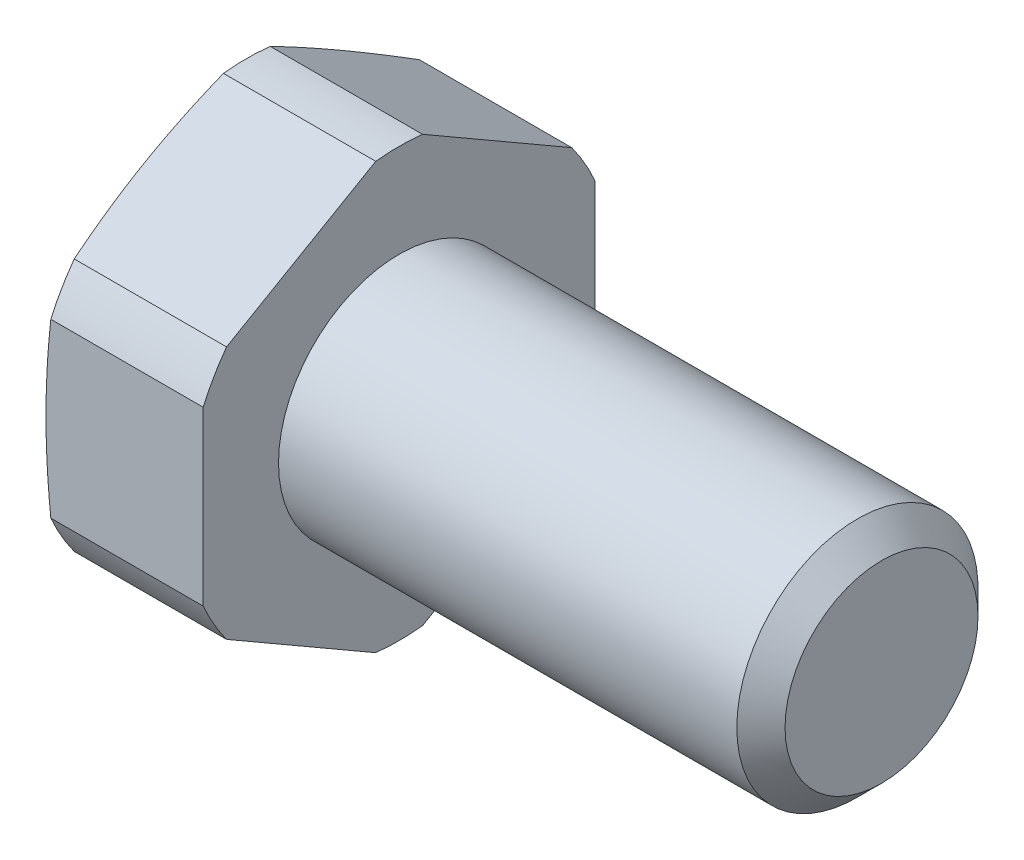
SolidWorks part; units mm, degrees
material "AISI 1020"
ref_plane "Спереди" through (0, 0, 0) normal (0, 0, 1) x (1, 0, 0)
ref_plane "Сверху" through (0, 0, 0) normal (0, 1, 0) x (1, 0, 0)
ref_plane "Справа" through (0, 0, 0) normal (1, 0, 0) x (0, 0, -1)
sketch "Эскиз1" plane through (0, 0, 0) normal (0, 0, 1) x (1, 0, 0)
  line L0 (-1000, 0) -> (49000, 0) construction
  line L1 (-5.3, 0) -> (-5.3, 6.175)
  line L2 (-5.3, 6.175) -> (-5.0521, 7.1)
  line L3 (-5.0521, 7.1) -> (0, 7.1)
  line L4 (0, 7.1) -> (0, 4)
  line L5 (0, 4) -> (15.2, 4)
  line L6 (16, 3.2) -> (16, 0)
  line L7 (16, 4) -> (16.625, 5.0825) construction
  line L8 (16.625, 5.0825) -> (17.25, 4) construction
  line L9 (17.25, 4) -> (16, 4) construction
  line L10 (16.625, 5.0825) -> (16.625, 4) construction
  line L11 (16.625, 5.0825) -> (0.625, 5.0825) construction
  line L12 (15.2, 4) -> (16, 3.2)
  line L13 (16, 4) -> (15.6, 3.6) construction
  line L14 (-5.3, 6.175) -> (-18.3, 6.175) construction
  line L15 (-5.3, 0) -> (16, 0)
  dimension "D1" = 0.8
  dimension "D2" = 15
revolve "Повернуть1" add sketch "Эскиз1" angle 360 about L0
cosmetic thread "Условное изображение резьбы1" parameters "D1"=16, "D2"=5.8349
sketch "Эскиз2" plane through (-5.3, 0, 0) normal (-1, 0, 0) x (0, 0, 1)
  line L1 (0, 7.5056) -> (-6.5, 3.7528)
  line L2 (-6.5, 3.7528) -> (-6.5, -3.7528)
  line L3 (-6.5, -3.7528) -> (0, -7.5056)
  line L4 (0, -7.5056) -> (6.5, -3.7528)
  line L5 (6.5, -3.7528) -> (6.5, 3.7528)
  line L6 (6.5, 3.7528) -> (0, 7.5056)
  circle A0 centre (0, 0) radius 6.5 construction
  dimension "D1" = 13
extrude "Вырез-Вытянуть1" cut sketch "Эскиз2" against normal up to surface (21.3 mm away) flip side to cut up to face at (16, 0, 3.2)
equation "\"D1@Эскиз1\"=\"_d_@Эскиз1\"/10"
equation "\"D@Эскиз1\"=\"S_@Эскиз1\"*0.95"
equation "\"D1@Эскиз2\"=\"S_@Эскиз1\""
equation "\"D1@Условное изображение резьбы1\"=\"b_@Эскиз1\""
equation "\"D2@Условное изображение резьбы1\"=\"_d_@Эскиз1\"-\"dr@Эскиз1\"*2"
